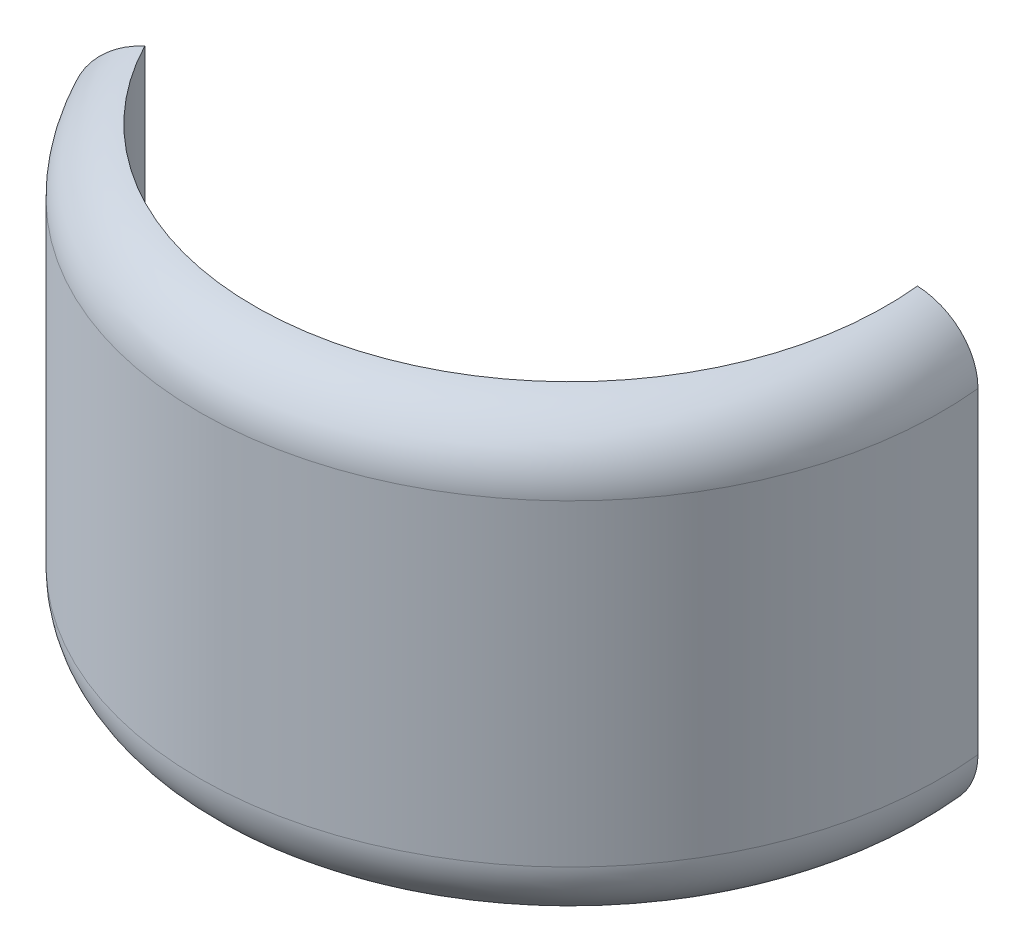
SolidWorks part; units mm, degrees
ref_plane "Front Plane" through (0, 0, 0) normal (0, 0, 1) x (1, 0, 0)
ref_plane "Top Plane" through (0, 0, 0) normal (0, 1, 0) x (1, 0, 0)
ref_plane "Right Plane" through (0, 0, 0) normal (1, 0, 0) x (0, 0, -1)
sketch "Sketch2" plane through (0, 0, 0) normal (0, 1, 0) x (1, 0, 0)
  line L0 (-19.5297, -0.8807) -> (-19.7731, -1.0068)
  line L1 (12.4696, 8.7367) -> (15.4528, 9.0539)
  line L2 (-22.164, -2.2455) -> (-19.7731, -1.0068)
  arc A0 (11.8186, 1.9577) -> (12.0122, 2.6396) centre (-4.4351, 6.9394) ccw
  arc A1 (11.5916, 1.2697) -> (11.8186, 1.9577) centre (-4.4351, 6.9394) ccw
  arc A2 (12.0122, 2.6396) -> (12.4696, 8.7367) centre (-4.4351, 6.9394) ccw
  arc A3 (-19.5297, -0.8807) -> (11.5916, 1.2697) centre (-4.4351, 6.9394) ccw
  circle A4 centre (-4.4351, 6.9394) radius 19.9668
extrude "Boss-Extrude1" add sketch "Sketch2" along normal blind 24 contours L2 A4 L1 A2 A0 A1 A3 L0 region at (-3.2331, 0, 10.456)
fillet "Fillet1" radius 3.5 2 edges at (1.312, 0, 12.1825) (1.312, 24, 12.1825)
